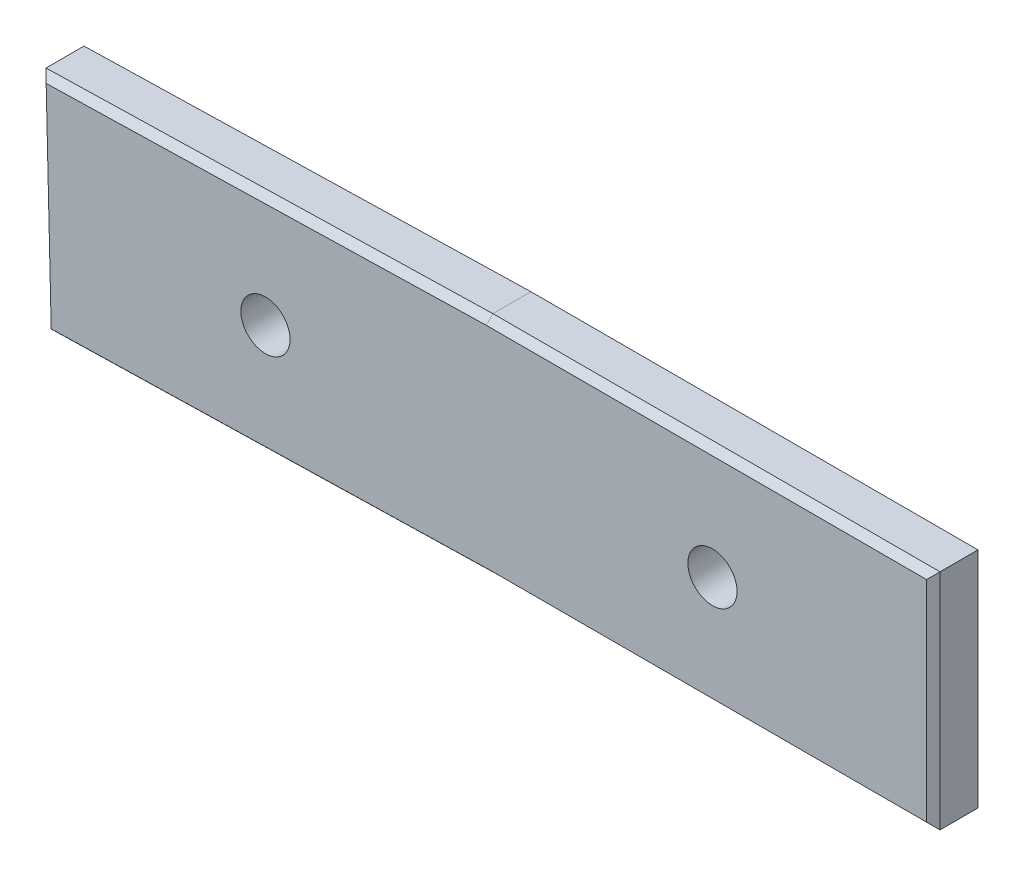
SolidWorks part; units mm, degrees
ref_plane "Front Plane" through (0, 0, 0) normal (0, 0, 1) x (1, 0, 0)
ref_plane "Top Plane" through (0, 0, 0) normal (0, 1, 0) x (1, 0, 0)
ref_plane "Right Plane" through (0, 0, 0) normal (1, 0, 0) x (0, 0, -1)
sketch "Sketch1" plane through (0, 0, 0) normal (0, 0, 1) x (1, 0, 0)
  line L0 (0, 0) -> (-499.8558, 0) construction
  line L1 (0, 0) -> (50, 0)
  line L2 (0, 0) -> (0, 44)
  line L3 (0, 44) -> (50, 44)
  line L4 (50, 0) -> (50, 44)
  line L5 (-499.8558, 0) -> (-500.6243, 31.9908)
  line L6 (-500.6243, 31.9908) -> (-0.7686, 44)
  line L7 (-499.8558, 0) -> (0, 12.0092)
  line L8 (0, 12.0092) -> (-0.7686, 44)
  line L9 (-500.3361, 19.9942) -> (-0.4804, 32.0035)
  line L10 (0, 32) -> (50, 32)
  line L11 (0, 12) -> (50, 12)
  dimension "D1" = 44
  dimension "D2" = 50
  dimension "D3" = 32
  dimension "D4" = 500
  dimension "D5" = 20
  dimension "D6" = 32
  dimension "D7" = 12
sketch "Sketch2" plane through (0, 0, 0) normal (0, 0, 1) x (1, 0, 0)
  line L0 (0, 12) -> (-40, 11.0482)
  line L1 (-499.8558, 0) -> (0, 12.0092) construction
  line L2 (-40, 11.0482) -> (-40, 0)
  line L3 (0, 0) -> (-499.8558, 0) construction
  line L4 (-40, 0) -> (0, 0)
  line L5 (0, 0) -> (0, 12)
  dimension "D1" = 40
sketch "Sketch3" plane through (0, 0, 0) normal (0, 0, 1) x (1, 0, 0)
  line L0 (-39.9885, 11.0485) -> (-40.4688, 31.0427)
  line L1 (-499.8558, 0) -> (0, 12.0092) construction
  line L2 (-500.3361, 19.9942) -> (-0.4804, 32.0035) construction
  line L3 (-40.4688, 31.0427) -> (-0.4804, 32.0035)
  line L4 (-0.4804, 32.0035) -> (39.5196, 32)
  line L5 (0, 32) -> (50, 32) construction
  line L7 (0, 12) -> (50, 12) construction
  line L8 (39.5196, 12) -> (0, 12)
  line L9 (0, 12) -> (-39.9885, 11.0485)
  line L10 (-40.2286, 21.0456) -> (-0.2402, 22.0063) construction
  line L11 (0, 12.0092) -> (-0.7686, 44) construction
  line L12 (39.5196, 32) -> (39.5196, 12)
  line L13 (39.5196, 22) -> (0, 22) construction
  line L14 (0, 0) -> (0, 44) construction
  circle A0 centre (19.7598, 22) radius 2.2
  circle A1 centre (-20.2344, 21.526) radius 2.2
  dimension "D3" = 4.4
  dimension "D1" = 40
  dimension "D2" = 40
extrude "Boss-Extrude1" add sketch "Sketch3" along normal blind 4
chamfer "Chamfer1" distance 0.6 angle 45 6 edges at (-40.2286, 21.0456, 4) (-20.4746, 31.5231, 4) (19.5196, 32.0017, 4) (39.5196, 22, 4) (19.7598, 12, 4) (-19.9942, 11.5242, 4)
